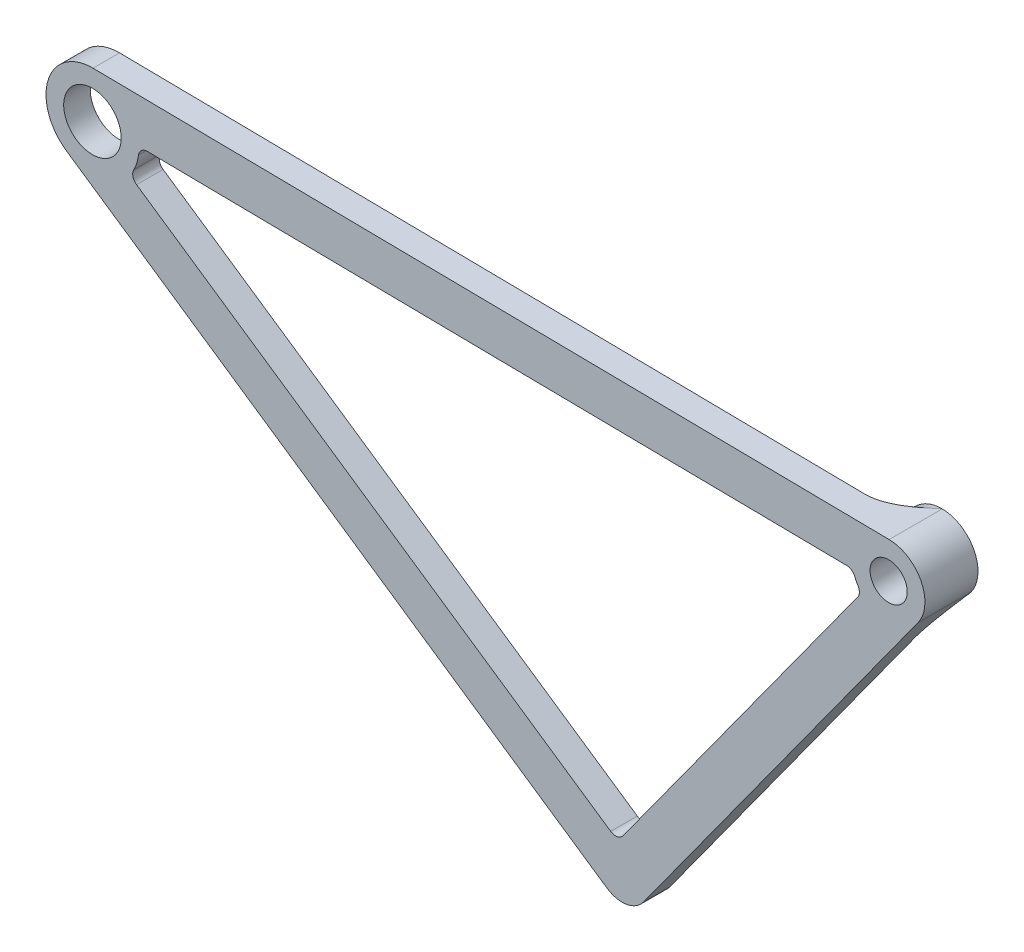
SolidWorks part; units mm, degrees
material "ABS"
ref_plane "Front Plane" through (0, 0, 0) normal (0, 0, 1) x (1, 0, 0)
ref_plane "Top Plane" through (0, 0, 0) normal (0, 1, 0) x (1, 0, 0)
ref_plane "Right Plane" through (0, 0, 0) normal (1, 0, 0) x (0, 0, -1)
sketch "Link Profile" plane through (0, 0, 0) normal (0, 0, 1) x (1, 0, 0)
  line L0 (-2.9553, -4.3392) -> (58.1785, -45.9757)
  line L1 (62.2973, -45.2554) -> (93.321, -2.4044)
  line L2 (90.0524, 4.0997) -> (0.0671, 5.2496)
  line L3 (0, 0) -> (59.8673, -43.4961) construction
  line L4 (0, 0) -> (90, 0) construction
  line L7 (59.3869, -40.7491) -> (4.1936, -3.1586)
  line L8 (85.9888, -0.8488) -> (5.2468, 0.183)
  line L9 (86.9253, -2.7122) -> (59.3869, -40.7491)
  line L10 (73.1561, -21.7307) -> (77.2061, -24.6628) construction
  line L11 (45.0597, 4.6746) -> (44.9958, -0.325) construction
  line L12 (27.6116, -25.1574) -> (30.4262, -21.0249) construction
  line L13 (92.1, 0) -> (94.1, 0) construction
  line L14 (-3.25, 0) -> (-5.25, 0) construction
  circle A0 centre (0, 0) radius 3.25
  circle A1 centre (90, 0) radius 2.1
  arc A2 (0.0671, 5.2496) -> (-2.9553, -4.3392) centre (0, 0) ccw
  arc A3 (93.321, -2.4044) -> (90.0524, 4.0997) centre (90, 0) ccw
  arc A4 (58.1785, -45.9757) -> (62.2973, -45.2554) centre (59.8673, -43.4961) ccw
  arc A5 (4.1936, -3.1586) -> (5.2468, 0.183) centre (0, 0) ccw
  arc A6 (86.9253, -2.7122) -> (85.9888, -0.8488) centre (90, 0) cw
  arc A9 (86.9253, -2.7122) -> (93.321, -2.4044) centre (90, 0) ccw construction
  arc A10 (-2.9553, -4.3392) -> (4.1936, -3.1586) centre (0, 0) ccw construction
  dimension "Joint A Diameter" = 6.5
  dimension "Joint B Diameter" = 4.2
  dimension "Foot Radius" = 3
  dimension "Link 2 Length" = 90
  dimension "Delta" = 36
  dimension "Leg Link Length" = 74
  dimension "Link Width" = 5
  dimension "Joint Wall Thickness" = 2
  dimension "D1" = 52.914
extrude "Link Extrude" add sketch "Link Profile" along normal mid plane 3
sketch "Sketch1" plane through (0, 0, -1.5) normal (0, 0, -1) x (-1, 0, 0)
  circle A0 centre (-90, 0) radius 4.1
  circle A1 centre (-90, 0) radius 2.1 construction
  circle A2 centre (-90, 0) radius 2.1
extrude "Boss-Extrude1" add sketch "Sketch1" along normal blind 3
fillet "Fillet1" radius 3 2 edges at (90.1971, -4.0953, -1.5) (86.8314, 2.6019, -1.5)
fillet "Fillet2" radius 1 5 edges at (4.1936, -3.1586, 0) (5.2468, 0.183, 0) (59.3869, -40.7491, 0) (85.9888, -0.8488, -1.5) (86.9253, -2.7122, -1.5)
equation "\"Link Length\"= 90"
equation "\"Delta\"= 36"
equation "\"Delta@Link Profile\"= \"Delta\""
equation "\"Link 2 Length@Link Profile\"= \"Link Length\""
equation "\"Joint A Diameter\"= 6.5"
equation "\"Joint B Diameter\"= 4.2"
equation "\"Joint A Diameter@Link Profile\"= \"Joint A Diameter\""
equation "\"Joint B Diameter@Link Profile\"= \"Joint B Diameter\""
equation "\"Leg Link Length\"= 74"
equation "\"Leg Link Length@Link Profile\"= \"Leg Link Length\""
equation "\"Joint B Extension\"= 3"
equation "\"D1@Boss-Extrude1\"=\"Joint B Extension\""
equation "\"D1@Fillet1\"=\"Joint B Extension\""
